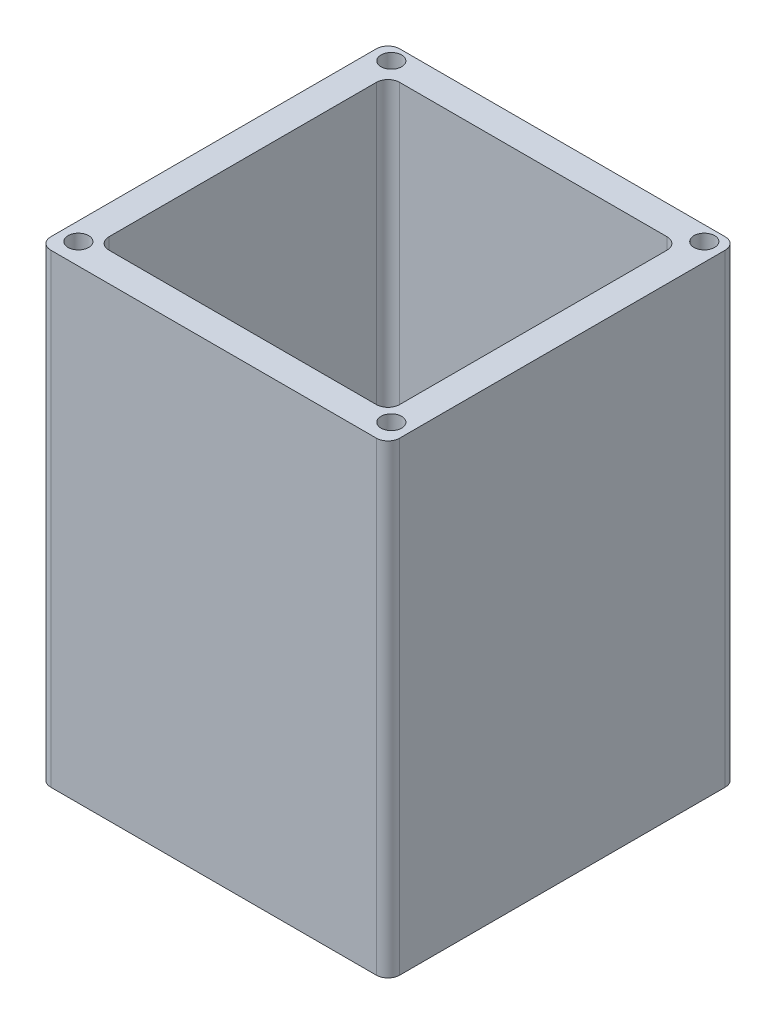
SolidWorks part; units mm, degrees
ref_plane "Front Plane" through (0, 0, 0) normal (0, 0, 1) x (1, 0, 0)
ref_plane "Top Plane" through (0, 0, 0) normal (0, 1, 0) x (1, 0, 0)
ref_plane "Right Plane" through (0, 0, 0) normal (1, 0, 0) x (0, 0, -1)
sketch "Sketch1" plane through (0, 0, 0) normal (0, 1, 0) x (1, 0, 0)
  line L1 (-35.56, -38.1) -> (35.56, -38.1)
  line L2 (-38.1, -35.56) -> (-38.1, 35.56)
  line L3 (-35.56, 38.1) -> (35.56, 38.1)
  line L4 (38.1, -35.56) -> (38.1, 35.56)
  line L5 (-38.1, -38.1) -> (38.1, 38.1) construction
  line L6 (-38.1, 38.1) -> (38.1, -38.1) construction
  arc A0 (-35.56, -38.1) -> (-38.1, -35.56) centre (-35.56, -35.56) cw
  arc A1 (35.56, -38.1) -> (38.1, -35.56) centre (35.56, -35.56) ccw
  arc A2 (35.56, 38.1) -> (38.1, 35.56) centre (35.56, 35.56) cw
  arc A3 (-38.1, 35.56) -> (-35.56, 38.1) centre (-35.56, 35.56) cw
  point P0 (0, 0)
  dimension "D3" = 2.54
  dimension "D1" = 76.2
  dimension "D2" = 76.2
extrude "Boss-Extrude1" add sketch "Sketch1" along normal blind 101.604
sketch "Sketch9" plane through (0, 101.604, 0) normal (0, 1, 0) x (1, 0, 0)
  line L0 (35.56, 38.1) -> (-35.56, 38.1) construction
  line L1 (-30.56, -33.1) -> (30.56, -33.1)
  line L2 (-33.1, -30.56) -> (-33.1, 30.56)
  line L3 (-30.56, 33.1) -> (30.56, 33.1)
  line L4 (33.1, -30.56) -> (33.1, 30.56)
  line L5 (-33.1, -33.1) -> (33.1, 33.1) construction
  line L6 (-33.1, 33.1) -> (33.1, -33.1) construction
  line L7 (38.1, -35.56) -> (38.1, 35.56) construction
  arc A0 (-30.56, -33.1) -> (-33.1, -30.56) centre (-30.56, -30.56) cw
  arc A1 (30.56, -33.1) -> (33.1, -30.56) centre (30.56, -30.56) ccw
  arc A2 (30.56, 33.1) -> (33.1, 30.56) centre (30.56, 30.56) cw
  arc A3 (-33.1, 30.56) -> (-30.56, 33.1) centre (-30.56, 30.56) cw
  point P0 (0, 0)
  dimension "D3" = 2.54
  dimension "D1" = 5
  dimension "D2" = 5
extrude "Cut-Extrude1" cut sketch "Sketch9" against normal blind 246.126
sketch "Sketch13" plane through (0, 0, -33.1) normal (0, 0, 1) x (1, 0, 0)
  line L1 (-20, 36.007) -> (20, 36.007)
  line L2 (-20, 36.007) -> (-20, 76.007)
  line L3 (-20, 76.007) -> (20, 76.007)
  line L4 (20, 36.007) -> (20, 76.007)
  line L5 (-20, 36.007) -> (20, 76.007) construction
  line L6 (-20, 76.007) -> (20, 36.007) construction
  point P0 (0, 56.007)
  dimension "D1" = 40
  dimension "D2" = 40
sketch "Sketch14" plane through (0, 101.604, 0) normal (0, 1, 0) x (1, 0, 0)
  line L2 (-38.1, -38.1) -> (38.1, -38.1)
  line L4 (-38.1, -38.1) -> (-38.1, 38.1)
  line L5 (-31.75, 31.75) -> (31.75, 31.75)
  line L6 (-31.75, 31.75) -> (-31.75, -31.75)
  line L7 (-31.75, -31.75) -> (31.75, -31.75)
  line L8 (31.75, 31.75) -> (31.75, -31.75)
  line L9 (-31.75, 31.75) -> (31.75, -31.75) construction
  line L10 (-31.75, -31.75) -> (31.75, 31.75) construction
  line L11 (-38.1, 38.1) -> (38.1, 38.1)
  line L12 (38.1, -38.1) -> (38.1, 38.1)
  line L13 (-38.1, -38.1) -> (38.1, 38.1) construction
  line L14 (-38.1, 38.1) -> (38.1, -38.1) construction
  point P0 (0, 0)
  point P9 (0, 0)
extrude "Boss-Extrude3" add sketch "Sketch14" against normal blind 101.604
fillet "Fillet1" radius 2.54 8 edges at (31.75, 50.802, 31.75) (-31.75, 50.802, 31.75) (31.75, 50.802, -31.75) (-31.75, 50.802, -31.75) (-38.1, 50.802, -38.1) (-38.1, 50.802, 38.1) (38.1, 50.802, 38.1) (38.1, 50.802, -38.1)
sketch "Sketch16" plane through (0, 0, -38.1) normal (0, 0, -1) x (-1, 0, 0)
  line L0 (20, 36.007) -> (-20, 76.007) construction
  line L1 (-20, 36.007) -> (20, 36.007)
  line L2 (-20, 36.007) -> (-20, 76.007)
  line L3 (-20, 76.007) -> (20, 76.007)
  line L4 (20, 36.007) -> (20, 76.007)
  line L5 (-20, 36.007) -> (20, 76.007) construction
  line L6 (-20, 76.007) -> (20, 36.007) construction
  point P0 (0, 56.007)
extrude "Cut-Extrude2" cut sketch "Sketch16" against normal blind 2.5
sketch "Sketch17" plane through (0, 101.604, 0) normal (0, 1, 0) x (1, 0, 0)
  point P0 (-34.1811, 34.9064)
  point P3 (34.1811, 34.9064)
  point P6 (34.1811, -33.4557)
  point P9 (-34.1811, -33.4557)
hole_wizard "M4 Clearance Hole1" positions "Sketch17" profile "Sketch18" hole size "M4" standard "ANSI Metric"
sketch "Sketch18" plane through (-34.1811, 101.604, -34.9064) normal (1, 0, 0) x (0, 0, 1)
  line L0 (0, 0) -> (0, 15.3219)
  line L1 (0, 15.3219) -> (2.25, 13.97)
  line L2 (2.25, 13.97) -> (2.25, 0)
  line L5 (2.25, 0) -> (0, 0)
  line L10 (0, 15.3219) -> (-2.25, 13.97) construction
  line L11 (0, -6.35) -> (0, 107.95) construction
  dimension "Hole Dia." = 4.5
  dimension "Hole Depth" = 13.97
  dimension "Drill Angle" = 118
sketch "Sketch21" plane through (38.1, 0, 0) normal (1, 0, 0) x (0, 0, -1)
  circle A0 centre (0, 76.708) radius 10
  circle A1 centre (0, 33.7027) radius 10
  dimension "D2" = 20
  dimension "D3" = 20
sketch "Sketch22" plane through (0, 0, 0) normal (0, -1, 0) x (-1, 0, 0)
sketch "Sketch24" plane through (0, 0, 0) normal (0, -1, 0) x (-1, 0, 0)
  point P0 (-34.1811, 34.1811)
  point P2 (34.1811, 34.1811)
  point P4 (34.1811, -34.1811)
  point P6 (-34.1811, -34.1811)
hole_wizard "M4 Clearance Hole2" positions "Sketch24" profile "Sketch23" hole size "M4" standard "ANSI Metric"
sketch "Sketch23" plane through (34.1811, 0, -34.1811) normal (1, 0, 0) x (0, 0, -1)
  line L0 (0, 0) -> (0, 15.3219)
  line L1 (0, 15.3219) -> (2.25, 13.97)
  line L2 (2.25, 13.97) -> (2.25, 0)
  line L5 (2.25, 0) -> (0, 0)
  line L10 (0, 15.3219) -> (-2.25, 13.97) construction
  line L11 (0, -6.35) -> (0, 107.95) construction
  dimension "Hole Dia." = 4.5
  dimension "Hole Depth" = 13.97
  dimension "Drill Angle" = 118
